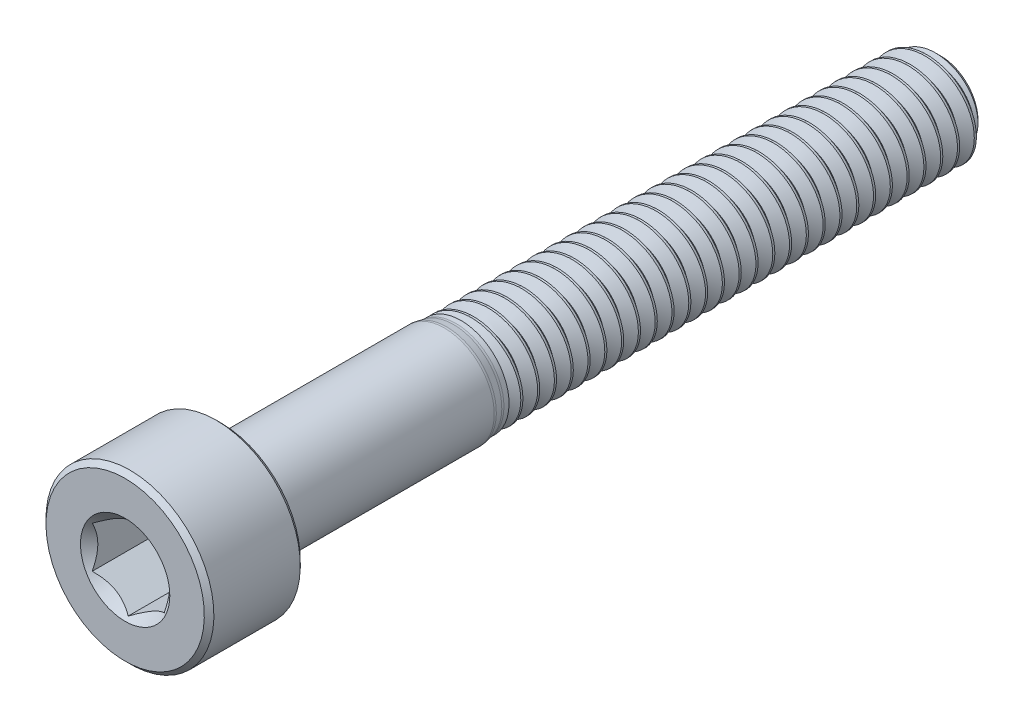
SolidWorks part; units mm, degrees
material "Alloy Steel"
ref_plane "Front Plane" through (0, 0, 0) normal (0, 0, 1) x (1, 0, 0)
ref_plane "Top Plane" through (0, 0, 0) normal (0, 1, 0) x (1, 0, 0)
ref_plane "Right Plane" through (0, 0, 0) normal (1, 0, 0) x (0, 0, -1)
sketch "Sketch1" plane through (0, 0, 0) normal (1, 0, 0) x (0, 0, -1)
  line L0 (-17, 0) -> (17, 0) construction
  line L1 (17, 0) -> (17, 1.5453) construction
  line L2 (17, 1.5453) -> (16.5453, 2) construction
  line L3 (16.5453, 2) -> (16.475, 2) construction
  line L4 (16.475, 2) -> (-13, 2) construction
  line L5 (-13, 2) -> (-13, 3.5) construction
  line L6 (-13, 3.5) -> (-17, 3.5) construction
  line L7 (-17, 3.5) -> (-17, 0) construction
  line L8 (17, 1.5453) -> (17, 2) construction
  line L9 (16.9563, 2.0758) -> (17.3062, 1.4696) construction
  line L10 (17.3062, 1.4696) -> (17.6562, 2.0758) construction
  line L11 (17.6562, 2.0758) -> (16.9563, 2.0758) construction
  line L12 (17.3062, 2.0758) -> (17.3062, 2) construction
  line L13 (17.3062, 1.4696) -> (17.3062, 1.5453) construction
  line L14 (17.2625, 1.5453) -> (17.35, 1.5453) construction
  line L15 (17, 2) -> (17.6125, 2) construction
  line L16 (16.9781, 2.0379) -> (17.6344, 2.0379) construction
  line L17 (17, 0) -> (17, -2) construction
  line L18 (-13.2, 3.5) -> (-13, 3.3) construction
  line L19 (-16.8, 3.5) -> (-17, 3.3) construction
  line L20 (-13, 2) -> (-13, 0) construction
  line L21 (-13, 1) -> (-3, 1) construction
  line L22 (-3, 1) -> (7, 1) construction
  line L23 (7, 1) -> (17, 1) construction
  line L24 (-3, 1) -> (-3, 2) construction
  line L25 (-3, 2) -> (-3, 3.5) construction
  line L26 (7, 1) -> (7, 3.5) construction
  point P0 (-17, 1.5)
  point P3 (15.25, 2)
  point P4 (0, 0)
  point P18 (7, 2)
  point P22 (17.3062, 1.5453)
  point P24 (16.475, 2)
  point P25 (17.3062, 2)
  point P28 (17.3062, 2.0379)
  point P29 (15.25, -2)
  point P30 (-3, 2)
  point P31 (-15, 3.5)
  point P37 (-13.7, 3.5)
  point P38 (-16.7, 3.5)
  point P45 (-3, 1)
  point P46 (7, 1)
  point P49 (-3, 2)
  dimension "D1" = 45
  dimension "D2" = 0.0875
  dimension "D7" = 0.2
  dimension "D8" = 0.2
  dimension "D9" = 0.2
  dimension "D10" = 0.1
  dimension "D11" = 0.5
  dimension "Drive Size" = 3
  dimension "Head Diameter" = 7
  dimension "Head Height" = 4
  dimension "Thread Pitch" = 0.7
  dimension "Thread Dia" = 4
  dimension "Length" = 30
  dimension "D12" = 0.525
  dimension "D4" = 1.75
  dimension "Minimum Thread Length" = 20
  dimension "D3" = 10
sketch "Sketch2" plane through (0, 0, 0) normal (1, 0, 0) x (0, 0, -1)
  line L0 (-17, 0) -> (-17, 3.3)
  line L1 (-16.8, 3.5) -> (-13.2, 3.5)
  line L2 (-13, 3.3) -> (-13, 2.2758)
  line L4 (16.5453, 2) -> (17, 1.5453)
  line L5 (17, 1.5453) -> (17, 0)
  line L6 (-13, 3.5) -> (-17, 3.5) construction
  line L7 (17, 0) -> (-17, 0)
  line L8 (-16.8, 3.5) -> (-17, 3.3) construction
  line L10 (-16.8, 3.5) -> (-17, 3.3)
  line L14 (-13.2, 3.5) -> (-13, 3.3) construction
  line L16 (-13.2, 3.5) -> (-13, 3.3)
  line L17 (-13, 2) -> (-13, 3.5) construction
  line L18 (-12.8, 2.0758) -> (-3.6927, 2.0758)
  line L19 (-3.2133, 2) -> (16.5453, 2)
  line L20 (16.475, 2) -> (-13, 2) construction
  line L21 (-3.5952, 2.0662) -> (-3.3108, 2.0096)
  line L22 (17.6562, 2.0758) -> (16.9563, 2.0758) construction
  arc A1 (-13, 2.2758) -> (-12.8, 2.0758) centre (-12.8, 2.2758) ccw
  arc A2 (-3.6927, 2.0758) -> (-3.5952, 2.0662) centre (-3.6927, 1.5758) cw
  arc A3 (-3.3108, 2.0096) -> (-3.2133, 2) centre (-3.2133, 2.5) ccw
  point P39 (-3.2625, 2)
  dimension "D3" = 0.2
  dimension "D6" = 0.5
  dimension "D4" = 11.25
  dimension "D5" = 0.2625
revolve "Revolve1" add sketch "Sketch2" angle 360 about L7
sketch "Sketch3" plane through (0, 0, 17) normal (0, 0, 1) x (1, 0, 0)
  line L1 (1.5, -0.866) -> (1.5, 0.866)
  line L2 (1.5, 0.866) -> (0, 1.7321)
  line L3 (0, 1.7321) -> (-1.5, 0.866)
  line L4 (-1.5, 0.866) -> (-1.5, -0.866)
  line L5 (-1.5, -0.866) -> (0, -1.7321)
  line L6 (0, -1.7321) -> (1.5, -0.866)
  circle A0 centre (0, 0) radius 1.5 construction
  circle A1 centre (0, 0) radius 3.5 construction
  circle A2 centre (0, 0) radius 3.5 construction
  circle A3 centre (0, 0) radius 1.7321 construction
  dimension "D1" = 3.4641
extrude "Cut-Extrude1" cut sketch "Sketch3" against normal offset from surface (3 mm away) 1 up to face at (0, 3.3, 13)
sketch "Sketch4" plane through (0, 0, 17) normal (0, 0, 1) x (1, 0, 0)
  circle A0 centre (0, 0) radius 1.862
  dimension "D1" = 3.7239
extrude "Cut-Extrude2" cut sketch "Sketch4" against normal up to vertex (2 mm away) draft 45 up to point (0, 3.5, 15)
sketch "Sketch11" plane through (0, 0, 0) normal (1, 0, 0) x (0, 0, -1)
  line L0 (-17, 0) -> (17, 0) construction
  line L1 (-17, 0) -> (17, 0) construction
  line L2 (-11.75, 0) -> (-11.75, 2) construction
  line L3 (16.475, 2) -> (-13, 2) construction
  line L4 (-4.9427, 0) -> (-4.9427, 2) construction
  point P2 (-11.75, 0)
  point P3 (-4.9427, 0)
  dimension "D1" = 1.25
  dimension "D2" = 1.25
sketch "Sketch6" plane through (0, 0, -17) normal (0, 0, -1) x (-1, 0, 0)
  circle A0 centre (0, 0) radius 2
curve "Helix/Spiral1" pitch 0.7 height 20.7 turns 29.5714
sketch "Sketch10" plane through (0, 0, 0) normal (1, 0, 0) x (0, 0, -1)
  line L0 (-3, -2) -> (-3, 2)
  line L2 (-17, 0) -> (17, 0) construction
  point P3 (-3, 0)
split "Split1" trim tools "Sketch10" bodies to split 106 resulting bodies 114 115
sketch "Sketch7" plane through (0, 0, 0) normal (1, 0, 0) x (0, 0, -1)
  line L0 (16.9781, 2.0379) -> (17.6344, 2.0379)
  line L1 (17.6344, 2.0379) -> (17.35, 1.5453)
  line L2 (17.35, 1.5453) -> (17.2625, 1.5453)
  line L3 (17.2625, 1.5453) -> (16.9781, 2.0379)
sweep "Cut-Sweep1" cut profiles "Sketch7" path "Helix/Spiral1" align with end faces yes
sketch "Sketch8" plane through (0, 0, 0) normal (1, 0, 0) x (0, 0, -1)
  line L0 (-13, 0) -> (-13, 2)
  line L2 (-13, 2) -> (-3, 2)
  line L4 (-3, 2) -> (-1.8453, 0)
  line L5 (-1.8453, 0) -> (-13, 0)
  line L6 (16.475, 2) -> (-13, 2) construction
  line L7 (-17, 0) -> (17, 0) construction
  dimension "D1" = 60
  dimension "D2" = 20
revolve "Revolve2" add sketch "Sketch8" angle 360 about L5
equation "\"D2@Sketch1\" = \"Thread Pitch@Sketch1\" / 8"
equation "\"D4@Helix/Spiral1\" = \"Thread Pitch@Sketch1\""
equation "\"D7@Sketch1\" = \"Head Height@Sketch1\" * .05"
equation "\"D8@Sketch1\"=\"D7@Sketch1\""
equation "\"D9@Sketch1\"=\"D7@Sketch1\""
equation "\"D10@Sketch1\"=\"D7@Sketch1\"/2"
equation "\"D11@Sketch1\"=\"D10@Sketch1\"*5"
equation "\"D4@Sketch1\"=\"Thread Pitch@Sketch1\"*2.5"
equation "\"D12@Sketch1\"=\"Thread Pitch@Sketch1\"*.75"
equation "\"D3@Helix/Spiral1\"=\"Minimum Thread Length@Sketch1\"+\"Thread Pitch@Sketch1\""
equation "\"D2@Sketch8\"=\"Minimum Thread Length@Sketch1\""
equation "\"D3@Sketch2\"=\"Thread Dia@Sketch1\"*0.05"
equation "\"D5@Sketch2\"=\"D12@Sketch1\"*0.5"
equation "\"D6@Sketch2\"=\"Thread Dia@Sketch1\"*0.125"
equation "\"D1@Sketch11\"=\"D3@Sketch1\"*0.125"
equation "\"D2@Sketch11\"=\"D1@Sketch11\""
equation "\"D1@Sketch4\"=\"D1@Sketch3\"*1.075"
